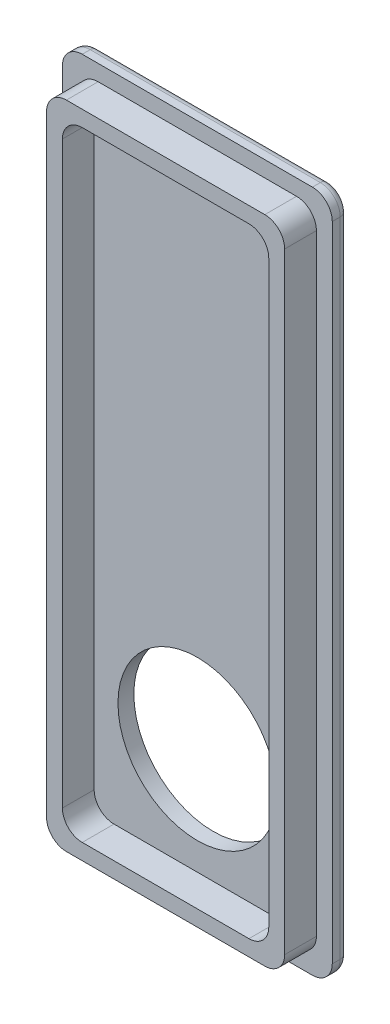
SolidWorks part; units mm, degrees
ref_plane "Plan de face" through (0, 0, 0) normal (0, 0, 1) x (1, 0, 0)
ref_plane "Plan de dessus" through (0, 0, 0) normal (0, 1, 0) x (1, 0, 0)
ref_plane "Plan de droite" through (0, 0, 0) normal (1, 0, 0) x (0, 0, -1)
sketch "Esquisse1" plane through (0, 0, 0) normal (0, 0, 1) x (1, 0, 0)
  line L1 (17, -43) -> (-17, -43)
  line L2 (17, -43) -> (17, 43)
  line L3 (17, 43) -> (-17, 43)
  line L4 (-17, -43) -> (-17, 43)
  line L5 (17, -43) -> (-17, 43) construction
  line L6 (17, 43) -> (-17, -43) construction
  point P0 (0, 0)
  dimension "D1" = 34
  dimension "D2" = 86
extrude "Boss.-Extru.1" add sketch "Esquisse1" along normal blind 2
sketch "Esquisse2" plane through (0, 0, 2) normal (0, 0, 1) x (1, 0, 0)
  line L1 (15, -41) -> (-15, -41)
  line L2 (15, -41) -> (15, 41)
  line L3 (15, 41) -> (-15, 41)
  line L4 (-15, -41) -> (-15, 41)
  line L5 (15, -41) -> (-15, 41) construction
  line L6 (15, 41) -> (-15, -41) construction
  line L7 (13, -39) -> (-13, -39)
  line L8 (13, -39) -> (13, 39)
  line L9 (13, 39) -> (-13, 39)
  line L10 (-13, -39) -> (-13, 39)
  line L11 (13, -39) -> (-13, 39) construction
  line L12 (13, 39) -> (-13, -39) construction
  point P0 (0, 0)
  point P6 (0, 0)
  dimension "D1" = 30
  dimension "D2" = 82
  dimension "D3" = 26
  dimension "D4" = 78
extrude "Boss.-Extru.2" add sketch "Esquisse2" along normal blind 4
fillet "Congé3" radius 1 4 edges at (-17, 0, 0) (0, 43, 0) (0, -43, 0) (17, 0, 0)
fillet "Congé2" radius 2.5 16 edges at (-17, 43, 1.5) (-15, 41, 4) (17, 43, 1.5) (15, 41, 4) (17, -43, 1.5) (15, -41, 4) (-17, -43, 1.5) (-15, -41, 4) (-16.7071, -42.7071, 0.2929) (16.7071, -42.7071, 0.2929) (16.7071, 42.7071, 0.2929) (-16.7071, 42.7071, 0.2929) (13, -39, 4) (-13, -39, 4) (13, 39, 4) (-13, 39, 4)
sketch "Esquisse3" plane through (0, 0, 0) normal (0, 0, -1) x (-1, 0, 0)
  circle A0 centre (0, -25.5534) radius 10
  dimension "D1" = 20
extrude "Enlèv. mat.-Extru.1" cut sketch "Esquisse3" against normal blind 4
